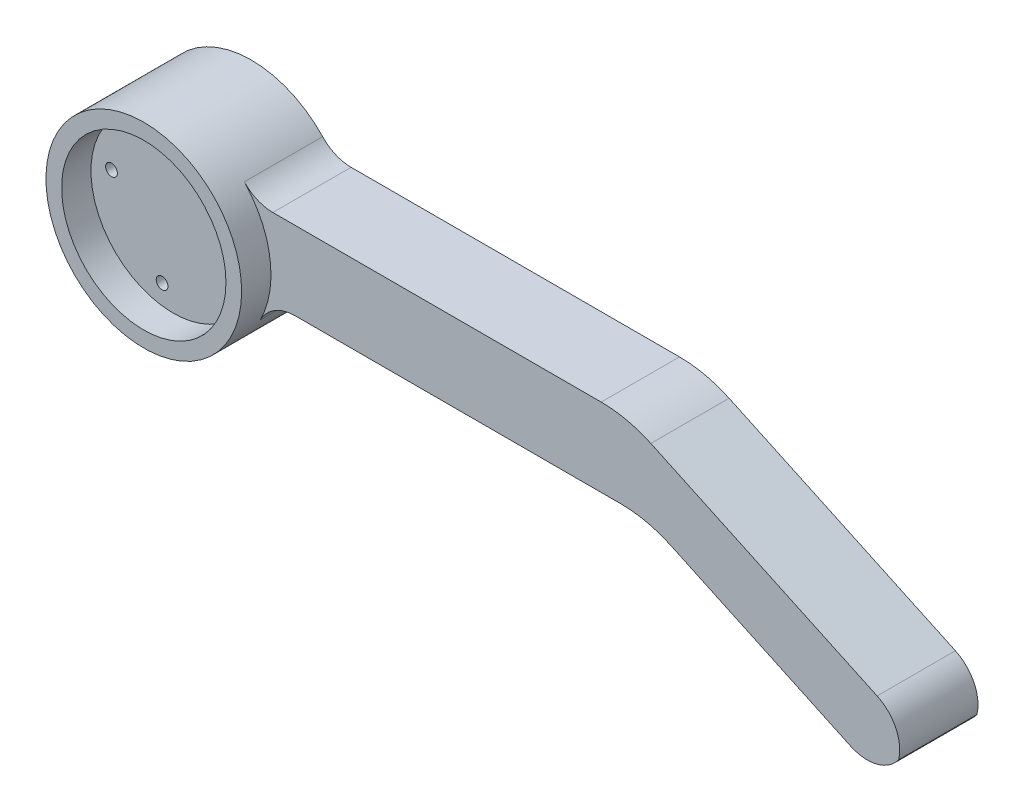
SolidWorks part; units mm, degrees
material "ABS"
ref_plane "Front" through (0, 0, 0) normal (0, 0, 1) x (1, 0, 0)
ref_plane "Top" through (0, 0, 0) normal (0, 1, 0) x (1, 0, 0)
ref_plane "Right" through (0, 0, 0) normal (1, 0, 0) x (0, 0, -1)
sketch "Esquisse1" plane through (0, 0, 0) normal (0, 0, 1) x (1, 0, 0)
  line L2 (10.3562, 7) -> (58.0156, 7)
  line L3 (12.1347, -3) -> (60.5311, -3)
  line L4 (58.0156, 7) -> (94.4722, -10)
  line L5 (94.4722, -10) -> (91.0913, -17.2505)
  line L6 (91.0913, -17.2505) -> (60.5311, -3)
  arc A0 (10.3562, 7) -> (12.1347, -3) centre (0, 0) ccw
  circle A2 centre (0, 0) radius 95 construction
  dimension "D1" = 12.5
  dimension "D4" = 10
  dimension "D5" = 7
  dimension "D9" = 190
  dimension "D2" = 10
  dimension "D3" = 8
  dimension "D8" = 25
extrude "Boss.-Extru.1" add sketch "Esquisse1" along normal mid plane 10
fillet "Congé4" radius 5 2 edges at (12.1347, -3, 0) (10.3562, 7, 0)
fillet "Congé3" radius 15 2 edges at (60.5311, -3, 0) (58.0156, 7, 0)
fillet "Congé6" radius 5 2 edges at (94.4722, -10, 0) (91.0913, -17.2505, 0) tangent propagation no
sketch "Sketch4" plane through (0, 0, -5) normal (0, 0, -1) x (-1, 0, 0)
  circle A0 centre (-1.4105, 7.8747) radius 0.75
  circle A1 centre (7.8747, 1.4105) radius 0.75
  circle A2 centre (1.4105, -7.8747) radius 0.75
  circle A3 centre (-7.8747, -1.4105) radius 0.75
  dimension "D1" = 1.5
  dimension "D2" = 4
extrude "Cut-Extrude5" cut sketch "Sketch4" against normal through all
sketch "Sketch5" plane through (0, 0, -5) normal (0, 0, -1) x (-1, 0, 0)
  circle A0 centre (0, 0) radius 10.5
  circle A1 centre (0, 0) radius 12.5
  dimension "D1" = 21
extrude "Boss-Extrude1" add sketch "Sketch5" against normal blind 3.75 from surface starting at face at (0.6605, 7.8747, 5)
equation "\"D3\" = \"D7@Esquisse8\""
